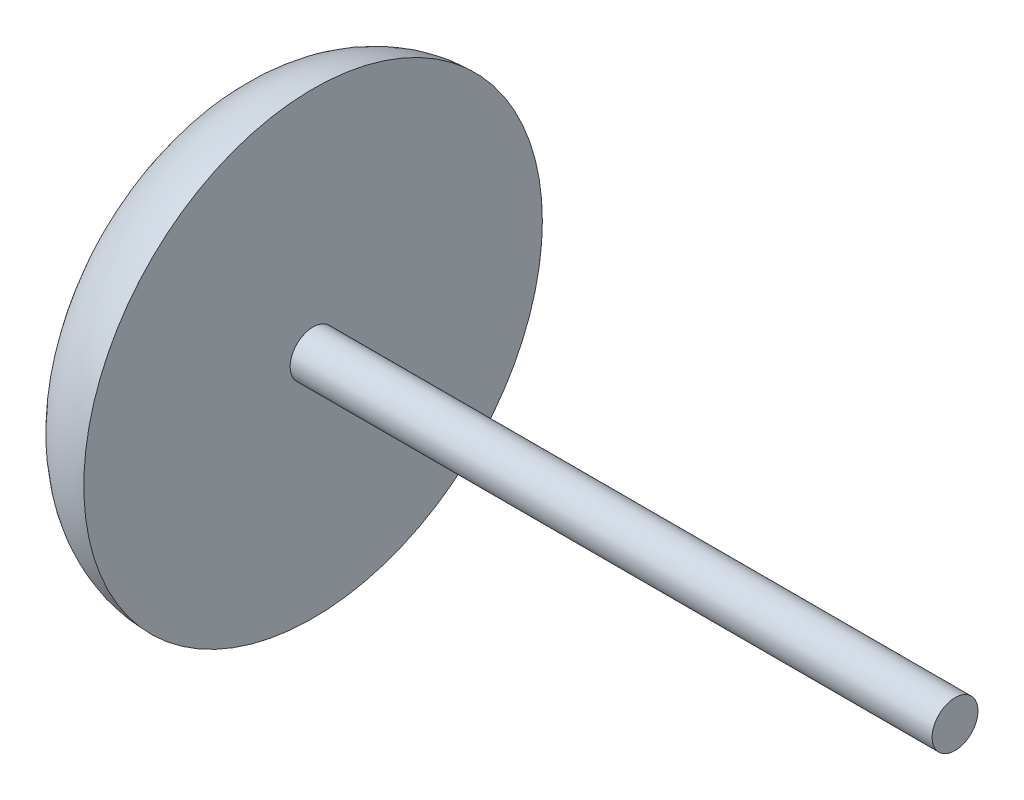
SolidWorks part; units mm, degrees
ref_plane "Ön Düzlem" through (0, 0, 0) normal (0, 0, 1) x (1, 0, 0)
ref_plane "Üst Düzlem" through (0, 0, 0) normal (0, 1, 0) x (1, 0, 0)
ref_plane "Sağ Düzlem" through (0, 0, 0) normal (1, 0, 0) x (0, 0, -1)
sketch "Sketch1" plane through (0, 0, 0) normal (1, 0, 0) x (0, 0, -1)
  circle A0 centre (0, 0) radius 25
extrude "Boss-Extrude1" add sketch "Sketch1" along normal blind 110
sketch "Sketch2" plane through (110, 0, 0) normal (1, 0, 0) x (0, 0, -1)
  circle A0 centre (0, 0) radius 2.5
  circle A1 centre (0, 0) radius 25
extrude "Cut-Extrude1" cut sketch "Sketch2" against normal blind 100
fillet "Fillet1" radius 10 1 edges at (0, 0, -25)
sketch "Sketch3" plane through (110, 0, 0) normal (1, 0, 0) x (0, 0, -1)
  circle A0 centre (0, 0) radius 2.5
extrude "Cut-Extrude2" cut sketch "Sketch3" against normal blind 30
